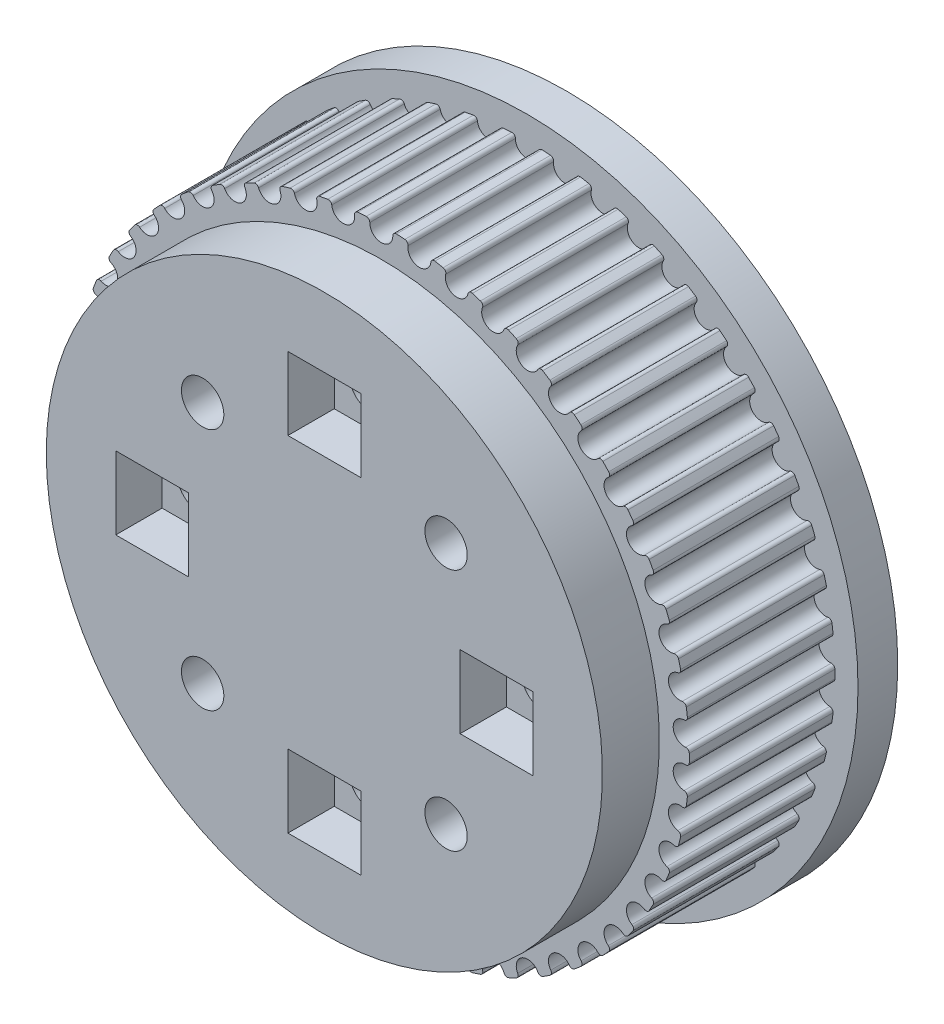
SolidWorks part; units mm, degrees
ref_plane "Front Plane" through (0, 0, 0) normal (1, 0, 0) x (0, 1, 0)
ref_plane "Top Plane" through (0, 0, 0) normal (0, 0, 1) x (0, 1, 0)
ref_plane "Right Plane" through (0, 0, 0) normal (0, 1, 0) x (-1, 0, 0)
sketch "Sketch1" plane through (0, 0, 0) normal (0, 0, 1) x (0, 1, 0)
  line L0 (0, 0) -> (0, 23.2582)
  line L1 (0, 0) -> (1.3869, 22.0447) construction
  line L2 (1.3869, 22.0447) -> (1.4416, 22.9129) construction
  line L3 (2.915, 23.0748) -> (0, 0)
  arc A1 (0.6393, 23.2495) -> (2.2797, 23.1462) centre (1.4416, 22.9129) ccw
  arc A2 (0, 23.2582) -> (0.6393, 23.2495) centre (0, 0) cw
  arc A3 (2.915, 23.0748) -> (2.2797, 23.1462) centre (0, 0) ccw
  dimension "D1" = 3.6
  dimension "D2" = 23.2582
extrude "Boss-Extrude1" add sketch "Sketch1" along normal blind 11 from offset 3
fillet "Fillet1" radius 0.26 2 edges at (-23.2495, 0.6393, 8.5) (-23.1462, 2.2797, 8.5)
pattern_circular "CirPattern1" count 50 over 360 about axis through (0, 0, 14) along (0, 0, -1) of "Fillet1", "Boss-Extrude1"
sketch "Sketch2" plane through (0, 0, 0) normal (0, 0, 1) x (0, 1, 0)
  circle A0 centre (0, 0) radius 25
  circle A1 centre (0, 0) radius 21
  dimension "D1" = 50
  dimension "D2" = 42
extrude "Boss-Extrude2" add sketch "Sketch2" along normal up to surface (3 mm away) contours A1 | A0 A1 region at (0, -24.2929, 0) region at (0, 0, 0) up to face at (0, 0, 3)
extrude "Boss-Extrude3" add sketch "Sketch2<3>" along normal blind 4.3 from surface contours A1 region at (0, 0, 0) starting at face at (0, 0, 14)
sketch "Sketch2<3>" plane through (0, 0, 0) normal (0, 0, 1) x (0, 1, 0) same geometry as "Sketch2"
sketch "Sketch3" plane through (0, 0, 18.3) normal (0, 0, 1) x (1, 0, 0)
  line L0 (15.75, 2.75) -> (15.75, -2.75)
  line L1 (-2.75, 15.75) -> (2.75, 15.75)
  line L2 (-2.75, 15.75) -> (-2.75, 10.25)
  line L3 (-2.75, 10.25) -> (2.75, 10.25)
  line L4 (2.75, 15.75) -> (2.75, 10.25)
  line L5 (-2.75, 15.75) -> (2.75, 10.25) construction
  line L6 (-2.75, 10.25) -> (2.75, 15.75) construction
  line L7 (15.75, 2.75) -> (10.25, 2.75)
  line L8 (10.25, 2.75) -> (10.25, -2.75)
  line L9 (15.75, -2.75) -> (10.25, -2.75)
  line L10 (15.75, 2.75) -> (10.25, -2.75) construction
  line L11 (10.25, 2.75) -> (15.75, -2.75) construction
  line L12 (2.75, -15.75) -> (-2.75, -15.75)
  line L13 (2.75, -15.75) -> (2.75, -10.25)
  line L14 (2.75, -10.25) -> (-2.75, -10.25)
  line L15 (-2.75, -15.75) -> (-2.75, -10.25)
  line L16 (2.75, -15.75) -> (-2.75, -10.25) construction
  line L17 (2.75, -10.25) -> (-2.75, -15.75) construction
  line L18 (-15.75, -2.75) -> (-15.75, 2.75)
  line L19 (-15.75, -2.75) -> (-10.25, -2.75)
  line L20 (-10.25, -2.75) -> (-10.25, 2.75)
  line L21 (-15.75, 2.75) -> (-10.25, 2.75)
  line L22 (-15.75, -2.75) -> (-10.25, 2.75) construction
  line L23 (-10.25, -2.75) -> (-15.75, 2.75) construction
  circle A0 centre (0, 0) radius 13 construction
  circle A1 centre (0, 13) radius 1.6
  circle A10 centre (13, 0) radius 1.6
  circle A11 centre (0, -13) radius 1.6
  circle A12 centre (-13, 0) radius 1.6
  point P18 (0, 0)
  point P33 (0, 0)
  dimension "D1" = 26
  dimension "D2" = 3.2
  dimension "D3" = 5.5
  dimension "D4" = 4
extrude "Cut-Extrude1" cut sketch "Sketch3" against normal through all both and the other way through all contours A1 | A10 | A12 | A11 region at (0, 13, 18.3) region at (13, 0, 18.3) region at (0, -13, 18.3) region at (-13, 0, 18.3)
extrude "Cut-Extrude2" cut sketch "Sketch3<3>" against normal blind 3.5 and the other way through all contours A12 | A1 | L21 L18 L19 L20 A12 | L4 L1 L2 L3 A1 | L9 L0 L7 L8 A10 | L15 L12 L13 L14 A11 | A11 | A10 region at (15.6722, 0, 18.3) region at (0, 15.6722, 18.3) region at (0, -15.6722, 18.3) region at (-15.6722, 0, 18.3) region at (0, 13, 18.3) region at (13, 0, 18.3) region at (0, -13, 18.3) region at (-13, 0, 18.3)
sketch "Sketch3<3>" plane through (0, 0, 18.3) normal (0, 0, 1) x (1, 0, 0) same geometry as "Sketch3"
sketch "Sketch4" plane through (0, 0, 0) normal (0, 0, -1) x (1, 0, 0)
  line L0 (0, 0) -> (9.1924, 9.1924) construction
  line L1 (11.9424, -11.9424) -> (6.4424, -11.9424)
  line L2 (6.4424, 11.9424) -> (11.9424, 11.9424)
  line L3 (6.4424, 11.9424) -> (6.4424, 6.4424)
  line L4 (6.4424, 6.4424) -> (11.9424, 6.4424)
  line L5 (11.9424, 11.9424) -> (11.9424, 6.4424)
  line L6 (6.4424, 11.9424) -> (11.9424, 6.4424) construction
  line L7 (6.4424, 6.4424) -> (11.9424, 11.9424) construction
  line L8 (6.4424, -6.4424) -> (6.4424, -11.9424)
  line L9 (11.9424, -6.4424) -> (6.4424, -6.4424)
  line L10 (11.9424, -6.4424) -> (11.9424, -11.9424)
  line L11 (-11.9424, -11.9424) -> (-11.9424, -6.4424)
  line L12 (-6.4424, -6.4424) -> (-11.9424, -6.4424)
  line L13 (-6.4424, -11.9424) -> (-6.4424, -6.4424)
  line L14 (-6.4424, -11.9424) -> (-11.9424, -11.9424)
  line L15 (-11.9424, 11.9424) -> (-6.4424, 11.9424)
  line L16 (-6.4424, 6.4424) -> (-6.4424, 11.9424)
  line L17 (-11.9424, 6.4424) -> (-6.4424, 6.4424)
  line L18 (-11.9424, 6.4424) -> (-11.9424, 11.9424)
  circle A0 centre (0, 0) radius 13 construction
  circle A1 centre (9.1924, 9.1924) radius 1.6
  circle A2 centre (9.1924, -9.1924) radius 1.6
  circle A3 centre (-9.1924, -9.1924) radius 1.6
  circle A4 centre (-9.1924, 9.1924) radius 1.6
  point P31 (0, 0)
  dimension "D2" = 3.2
  dimension "D1" = 5.5
  dimension "D3" = 4
extrude "Cut-Extrude3" cut sketch "Sketch4" against normal through all contours A4 | A1 | A2 | A3 region at (9.1924, -9.1924, 0) region at (9.1924, 9.1924, 0) region at (-9.1924, 9.1924, 0) region at (-9.1924, -9.1924, 0)
extrude "Cut-Extrude4" cut sketch "Sketch4<3>" against normal blind 3
sketch "Sketch4<3>" plane through (0, 0, 0) normal (0, 0, -1) x (1, 0, 0) same geometry as "Sketch4"
equation "\"D2@Sketch1\"=(50*3) / (PI * 2) - 0.615"
